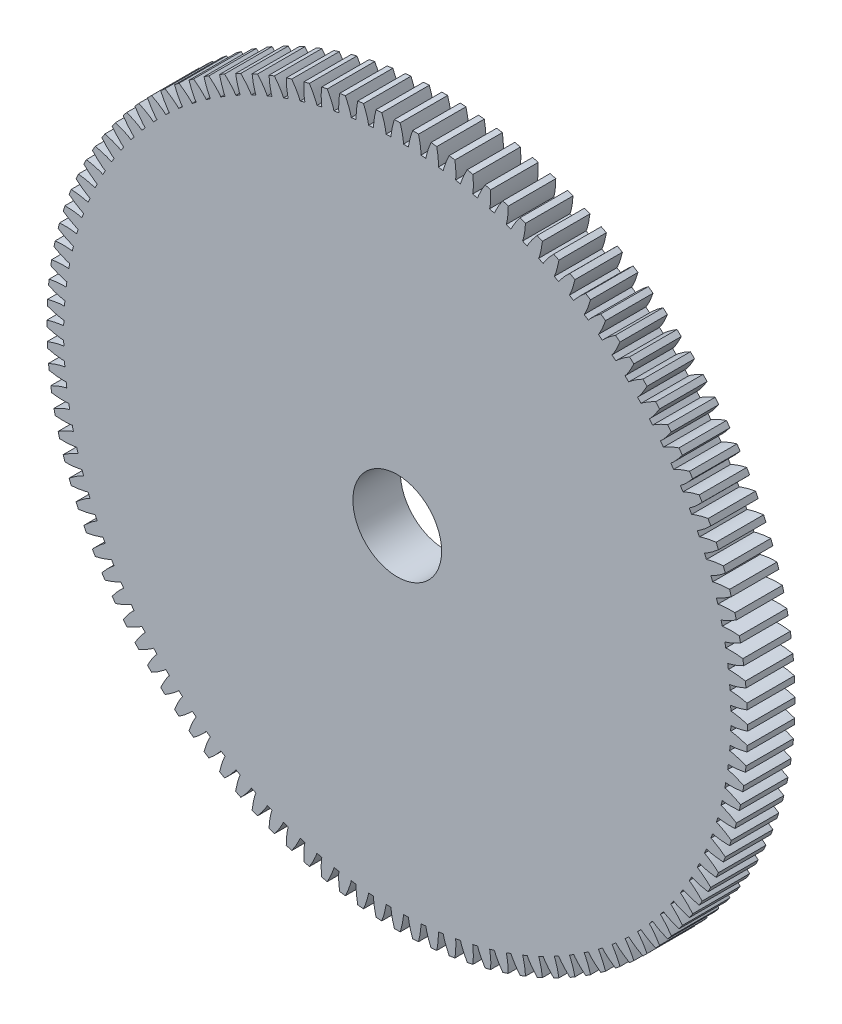
SolidWorks part; units mm, degrees
material "Brass"
ref_plane "Front Plane" through (0, 0, 0) normal (0, 0, 1) x (1, 0, 0)
ref_plane "Top Plane" through (0, 0, 0) normal (0, 1, 0) x (1, 0, 0)
ref_plane "Right Plane" through (0, 0, 0) normal (1, 0, 0) x (0, 0, -1)
sketch "Sketch1" plane through (0, 0, 0) normal (0, 0, 1) x (1, 0, 0)
  circle A0 centre (0, 0) radius 51.6467
extrude "Boss-Extrude1" add sketch "Sketch1" along normal blind 7
sketch "Sketch2" plane through (0, 0, 0) normal (0, 0, 1) x (1, 0, 0)
  circle A0 centre (0, 0) radius 6.5405
  dimension "D1" = 13.081
extrude "Cut-Extrude2" cut sketch "Sketch2" against normal blind 9 and the other way blind 9
sketch "Sketch3" plane through (0, 0, 0) normal (0, 0, 1) x (1, 0, 0)
  spline S0 degree 4 poles (49.1734, 0.9164) (49.1838, 0.9166) (49.2037, 0.9164) (49.236, 0.9157) (49.2811, 0.9138) (49.3345, 0.9109) (49.3975, 0.9065) (49.4669, 0.9007) (49.5426, 0.8933) (49.6181, 0.8849) (49.6937, 0.8757) (49.769, 0.8656) (49.8604, 0.8525) (49.9703, 0.8355) (50.099, 0.8136) (50.2454, 0.7864) (50.3952, 0.7562) (50.5429, 0.7245) (50.6927, 0.69) (50.8381, 0.655) (50.9896, 0.6161) (51.1298, 0.579) (51.2875, 0.5348) (51.415, 0.4982) (51.584, 0.4471) (51.6841, 0.416) (51.8014, 0.3786) (51.8537, 0.3614) (51.8859, 0.3509) knots 0 0 0 0 0 0.015084 0.028532 0.04661 0.064855 0.092111 0.119476 0.146842 0.174209 0.201575 0.228941 0.256307 0.307035 0.361767 0.4165 0.471232 0.525964 0.580697 0.635429 0.690161 0.744894 0.799626 0.854358 0.909091 0.954545 1 1 1 1 1 construction
  spline S1 degree 4 poles (49.1734, 0.9164) (49.1838, 0.9166) (49.2037, 0.9164) (49.236, 0.9157) (49.2811, 0.9138) (49.3345, 0.9109) (49.3975, 0.9065) (49.4669, 0.9007) (49.5426, 0.8933) (49.6181, 0.8849) (49.6937, 0.8757) (49.769, 0.8656) (49.8604, 0.8525) (49.9703, 0.8355) (50.099, 0.8136) (50.2454, 0.7864) (50.3952, 0.7562) (50.5429, 0.7245) (50.6927, 0.69) (50.8381, 0.655) (50.9896, 0.6161) (51.1298, 0.579) (51.2875, 0.5348) (51.415, 0.4982) (51.5474, 0.4582) (51.6119, 0.4383) (51.6449, 0.428) knots 0 0 0 0 0 0.015084 0.028532 0.04661 0.064855 0.092111 0.119476 0.146842 0.174209 0.201575 0.228941 0.256307 0.307035 0.361767 0.4165 0.471232 0.525964 0.580697 0.635429 0.690161 0.744894 0.799626 0.854358 0.909091 0.909091 0.909091 0.909091 0.909091
  spline S2 degree 4 poles (49.1539, 1.6583) (49.1644, 1.6588) (49.1842, 1.66) (49.2165, 1.6624) (49.2614, 1.6666) (49.3146, 1.6723) (49.3773, 1.68) (49.4463, 1.6894) (49.5214, 1.7008) (49.5965, 1.7131) (49.6714, 1.7263) (49.7461, 1.7403) (49.8367, 1.7581) (49.9455, 1.7809) (50.0729, 1.8095) (50.2177, 1.8443) (50.3657, 1.8823) (50.5116, 1.9217) (50.6594, 1.964) (50.8027, 2.0066) (50.952, 2.0533) (51.09, 2.0977) (51.2452, 2.1502) (51.3706, 2.1933) (51.5367, 2.2532) (51.635, 2.2895) (51.7503, 2.333) (51.8016, 2.3529) (51.8332, 2.3651) knots 0 0 0 0 0 0.015084 0.028532 0.04661 0.064855 0.092111 0.119476 0.146842 0.174209 0.201575 0.228941 0.256307 0.307035 0.361767 0.4165 0.471232 0.525964 0.580697 0.635429 0.690161 0.744894 0.799626 0.854358 0.909091 0.954545 1 1 1 1 1 construction
  spline S3 degree 4 poles (49.1539, 1.6583) (49.1644, 1.6588) (49.1842, 1.66) (49.2165, 1.6624) (49.2614, 1.6666) (49.3146, 1.6723) (49.3773, 1.68) (49.4463, 1.6894) (49.5214, 1.7008) (49.5965, 1.7131) (49.6714, 1.7263) (49.7461, 1.7403) (49.8367, 1.7581) (49.9455, 1.7809) (50.0729, 1.8095) (50.2177, 1.8443) (50.3657, 1.8823) (50.5116, 1.9217) (50.6594, 1.964) (50.8027, 2.0066) (50.952, 2.0533) (51.09, 2.0977) (51.2452, 2.1502) (51.3706, 2.1933) (51.5007, 2.2403) (51.5641, 2.2634) (51.5965, 2.2754) knots 0 0 0 0 0 0.015084 0.028532 0.04661 0.064855 0.092111 0.119476 0.146842 0.174209 0.201575 0.228941 0.256307 0.307035 0.361767 0.4165 0.471232 0.525964 0.580697 0.635429 0.690161 0.744894 0.799626 0.854358 0.909091 0.909091 0.909091 0.909091 0.909091
  spline S4 degree 4 poles (49.152, 1.7331) (49.1521, 1.7275) (49.1524, 1.7162) (49.1528, 1.7032) (49.1537, 1.6661) (49.1542, 1.6496) (49.1554, 1.6026) (49.1561, 1.5744) (49.1572, 1.5339) (49.158, 1.5022) (49.1589, 1.4673) (49.1598, 1.4358) (49.1606, 1.4032) (49.1615, 1.3704) (49.1623, 1.3377) (49.1632, 1.3038) (49.1641, 1.2685) (49.1651, 1.2321) (49.1661, 1.1947) (49.1671, 1.1572) (49.168, 1.1226) (49.1689, 1.0853) (49.1698, 1.0523) (49.1709, 1.0096) (49.1717, 0.9804) (49.1731, 0.927) (49.1735, 0.9094) (49.1745, 0.8714) (49.1749, 0.857) (49.1752, 0.847) (49.1753, 0.8418) knots 0 0 0 0 0 0.022088 0.044177 0.083333 0.119319 0.159813 0.201093 0.243304 0.280291 0.314751 0.350761 0.388774 0.424594 0.463227 0.497138 0.541352 0.583276 0.626202 0.666552 0.706902 0.743676 0.7856 0.828955 0.87417 0.916667 0.958835 0.979418 1 1 1 1 1 construction
  spline S5 degree 4 poles (49.1539, 1.6583) (49.1541, 1.6517) (49.1545, 1.6378) (49.1554, 1.6026) (49.1561, 1.5744) (49.1572, 1.5339) (49.158, 1.5022) (49.1589, 1.4673) (49.1598, 1.4358) (49.1606, 1.4032) (49.1615, 1.3704) (49.1623, 1.3377) (49.1632, 1.3038) (49.1641, 1.2685) (49.1651, 1.2321) (49.1661, 1.1947) (49.1671, 1.1572) (49.168, 1.1226) (49.1689, 1.0853) (49.1698, 1.0523) (49.1709, 1.0096) (49.1717, 0.9804) (49.1727, 0.94) (49.1732, 0.9243) (49.1734, 0.9164) knots 0.083333 0.083333 0.083333 0.083333 0.083333 0.119319 0.159813 0.201093 0.243304 0.280291 0.314751 0.350761 0.388774 0.424594 0.463227 0.497138 0.541352 0.583276 0.626202 0.666552 0.706902 0.743676 0.7856 0.828955 0.87417 0.916667 0.916667 0.916667 0.916667 0.916667
  spline S6 degree 4 poles (50.8043, 0.4211) (50.864, 0.4216) (50.9794, 0.4225) (51.1316, 0.4238) (51.5629, 0.4274) (51.7496, 0.4289) (52.3065, 0.4335) (52.6262, 0.4362) (53.0785, 0.4399) (53.4484, 0.443) (53.8676, 0.4465) (54.2464, 0.4496) (54.6546, 0.453) (55.0383, 0.4562) (55.4322, 0.4594) (55.8223, 0.4627) (56.2055, 0.4658) (56.6028, 0.4691) (56.9958, 0.4724) (57.4001, 0.4757) (57.7912, 0.479) (58.2102, 0.4825) (58.5784, 0.4855) (59.0365, 0.4893) (59.3484, 0.4919) (59.8904, 0.4964) (60.0774, 0.4979) (60.499, 0.5014) (60.6501, 0.5027) (60.7751, 0.5037) (60.8382, 0.5042) knots 0 0 0 0 0 0.020582 0.041165 0.083333 0.123922 0.164487 0.203919 0.245641 0.283463 0.324863 0.363448 0.401438 0.443624 0.479586 0.519794 0.557378 0.596758 0.637386 0.678142 0.716036 0.757316 0.79719 0.837516 0.878097 0.916667 0.955572 0.977786 1 1 1 1 1 construction
  spline S7 degree 4 poles (51.6449, 0.428) (51.7297, 0.4287) (51.8939, 0.4301) (52.3065, 0.4335) (52.6262, 0.4362) (53.0785, 0.4399) (53.4484, 0.443) (53.8676, 0.4465) (54.2464, 0.4496) (54.6546, 0.453) (55.0383, 0.4562) (55.4322, 0.4594) (55.8223, 0.4627) (56.2055, 0.4658) (56.6028, 0.4691) (56.9958, 0.4724) (57.4001, 0.4757) (57.7912, 0.479) (58.2102, 0.4825) (58.5784, 0.4855) (59.0365, 0.4893) (59.3484, 0.4919) (59.7573, 0.4953) (59.9173, 0.4966) (59.9978, 0.4973) knots 0.083333 0.083333 0.083333 0.083333 0.083333 0.123922 0.164487 0.203919 0.245641 0.283463 0.324863 0.363448 0.401438 0.443624 0.479586 0.519794 0.557378 0.596758 0.637386 0.678142 0.716036 0.757316 0.79719 0.837516 0.878097 0.916667 0.916667 0.916667 0.916667 0.916667
  spline S8 degree 4 poles (59.9992, 0.2811) (59.9991, 0.2966) (59.999, 0.3264) (59.9988, 0.3667) (59.998, 0.4759) (59.9976, 0.5237) (59.9963, 0.6646) (59.9953, 0.7445) (59.9938, 0.8601) (59.9923, 0.9543) (59.9905, 1.0614) (59.9887, 1.1607) (59.9866, 1.2646) (59.9844, 1.3658) (59.9819, 1.4686) (59.9794, 1.5706) (59.9766, 1.6727) (59.9736, 1.7754) (59.9706, 1.8766) (59.9672, 1.9805) (59.9639, 2.0797) (59.96, 2.1868) (59.9566, 2.2809) (59.952, 2.3964) (59.9488, 2.4763) (59.9428, 2.617) (59.9407, 2.6648) (59.9358, 2.7739) (59.9338, 2.8142) (59.9324, 2.844) (59.9317, 2.8594) knots 0 0 0 0 0 0.020959 0.041918 0.083333 0.123016 0.162698 0.202381 0.242063 0.281746 0.321429 0.361111 0.400794 0.440476 0.480159 0.519841 0.559524 0.599206 0.638889 0.678571 0.718254 0.757937 0.797619 0.837302 0.876984 0.916667 0.958082 0.979041 1 1 1 1 1 construction
  spline S9 degree 4 poles (59.9978, 0.4973) (59.9976, 0.5186) (59.9973, 0.5601) (59.9963, 0.6646) (59.9953, 0.7445) (59.9938, 0.8601) (59.9923, 0.9543) (59.9905, 1.0614) (59.9887, 1.1607) (59.9866, 1.2646) (59.9844, 1.3658) (59.9819, 1.4686) (59.9794, 1.5706) (59.9766, 1.6727) (59.9736, 1.7754) (59.9706, 1.8766) (59.9672, 1.9805) (59.9639, 2.0797) (59.96, 2.1868) (59.9566, 2.2809) (59.952, 2.3964) (59.9488, 2.4763) (59.9444, 2.5807) (59.9426, 2.6222) (59.9416, 2.6434) knots 0.083333 0.083333 0.083333 0.083333 0.083333 0.123016 0.162698 0.202381 0.242063 0.281746 0.321429 0.361111 0.400794 0.440476 0.480159 0.519841 0.559524 0.599206 0.638889 0.678571 0.718254 0.757937 0.797619 0.837302 0.876984 0.916667 0.916667 0.916667 0.916667 0.916667
  spline S10 degree 4 poles (60.7813, 2.6805) (60.7233, 2.6779) (60.6112, 2.673) (60.4593, 2.6663) (60.0264, 2.6472) (59.8505, 2.6394) (59.3125, 2.6157) (59.0208, 2.6028) (58.6061, 2.5846) (58.2603, 2.5693) (57.8595, 2.5516) (57.496, 2.5356) (57.0992, 2.5181) (56.7297, 2.5018) (56.3678, 2.4858) (56.0013, 2.4697) (55.6349, 2.4535) (55.2589, 2.4369) (54.8708, 2.4198) (54.4874, 2.4029) (54.084, 2.3851) (53.7043, 2.3684) (53.2954, 2.3503) (52.937, 2.3345) (52.5215, 2.3162) (52.2196, 2.3029) (51.696, 2.2798) (51.481, 2.2703) (51.015, 2.2498) (50.8906, 2.2443) (50.7566, 2.2384) knots 0 0 0 0 0 0.02008 0.040161 0.083333 0.123261 0.159319 0.197812 0.233027 0.26907 0.309878 0.349805 0.383268 0.424652 0.459253 0.493239 0.530412 0.57034 0.610222 0.64719 0.685114 0.729048 0.765971 0.80369 0.838967 0.877741 0.916667 0.958333 1 1 1 1 1 construction
  spline S11 degree 4 poles (59.9416, 2.6434) (59.8583, 2.6398) (59.7031, 2.6329) (59.3125, 2.6157) (59.0208, 2.6028) (58.6061, 2.5846) (58.2603, 2.5693) (57.8595, 2.5516) (57.496, 2.5356) (57.0992, 2.5181) (56.7297, 2.5018) (56.3678, 2.4858) (56.0013, 2.4697) (55.6349, 2.4535) (55.2589, 2.4369) (54.8708, 2.4198) (54.4874, 2.4029) (54.084, 2.3851) (53.7043, 2.3684) (53.2954, 2.3503) (52.937, 2.3345) (52.5215, 2.3162) (52.2196, 2.3029) (51.8371, 2.286) (51.6777, 2.279) (51.5965, 2.2754) knots 0.083333 0.083333 0.083333 0.083333 0.083333 0.123261 0.159319 0.197812 0.233027 0.26907 0.309878 0.349805 0.383268 0.424652 0.459253 0.493239 0.530412 0.57034 0.610222 0.64719 0.685114 0.729048 0.765971 0.80369 0.838967 0.877741 0.916667 0.916667 0.916667 0.916667 0.916667
extrude "Cut-Extrude4" cut sketch "Sketch3" against normal blind 8 and the other way blind 8
ref_axis "Axis1" through (0, 0, -0.35) along (0, 0, 1)
pattern_circular "CirPattern1" count 120 over 360 about axis through (0, 0, -0.35) along (0, 0, 1) of "Cut-Extrude4"
equation "\"TrigProbe\"= cos(60)"
equation "\"SqrProbe\"= sqr(2)"
equation "\"AtnProbe\"= atn(1)"
equation "\"ToothCount\" = 120"
equation "\"DP\"= 30"
equation "\"PA\"= 14.5"
equation "\"PArad\"= \"PA\" * 3.14159265358979 / 180"
equation "\"Rb\"= \"ToothCount\" / \"DP\" * cos(\"PA\") / 2"
equation "\"Ra\"= (\"ToothCount\" + 2) / \"DP\" / 2"
equation "\"Tmax\"= sqr(\"Ra\" * \"Ra\" / (\"Rb\" * \"Rb\") - 1)"
equation "\"Delta\"= 3.14159265358979 / (2 * \"ToothCount\") + tan(\"PA\") - \"PArad\""
equation "\"Gamma\"= 2 * 3.14159265358979 / \"ToothCount\""
equation "\"ThetaL\"= atn(\"Tmax\") * 3.14159265358979 / 180 - \"Tmax\" + \"Delta\""
equation "\"ThetaU\"= \"Tmax\" - atn(\"Tmax\") * 3.14159265358979 / 180 - \"Delta\" + \"Gamma\""
equation "\"D1@Sketch1\" = 2 * \"Ra\""
equation "\"BoreDia\" = 0.515"
equation "\"D1@Sketch2\" = \"BoreDia\""
equation "\"D1@CirPattern1\" = \"ToothCount\""
